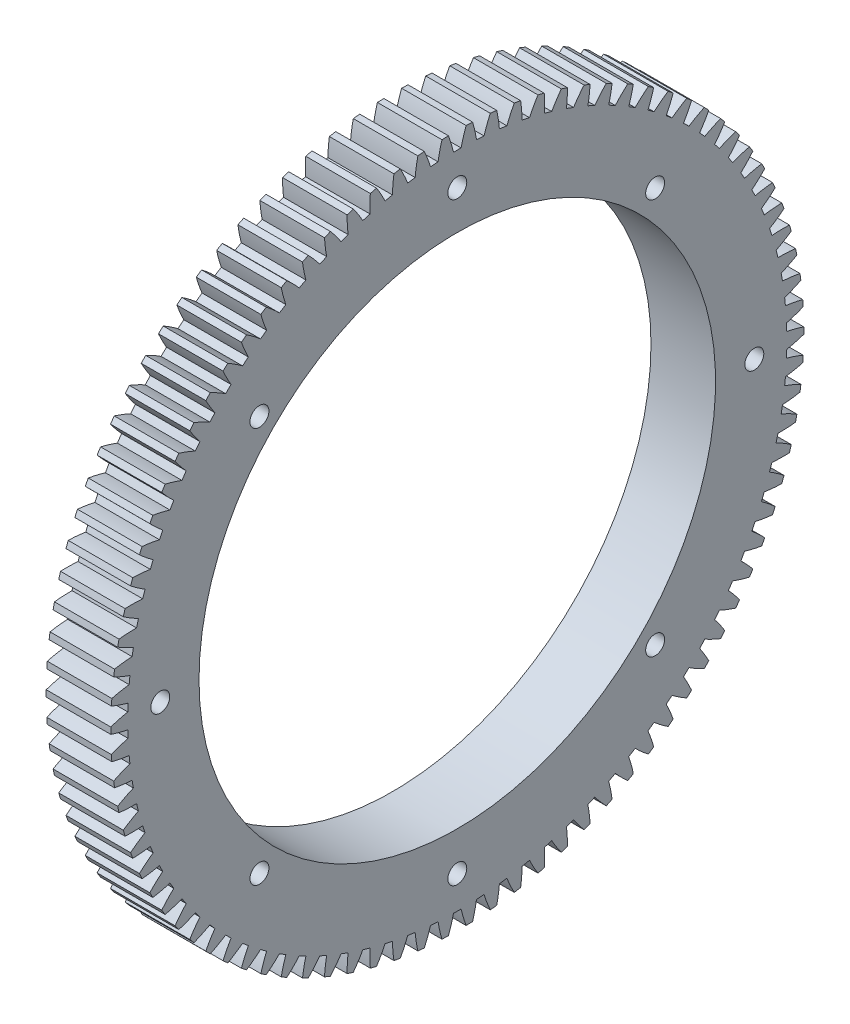
SolidWorks part; units mm, degrees
note: The reader was unsure of these and kept them because the rebuilt part matched: shared geometry of "Sketch1<4>", "Sketch1<5>".
ref_plane "Plane1" through (0, 0, 0) normal (0, 0, 1) x (1, 0, 0)
ref_plane "Plane2" through (0, 0, 0) normal (0, 1, 0) x (1, 0, 0)
ref_plane "Plane3" through (0, 0, 0) normal (1, 0, 0) x (0, 0, -1)
sketch "HoldingSke" plane through (0, 0, 0) normal (0, 1, 0) x (1, 0, 0)
  line L0 (0, 0) -> (0, -0.5714)
  line L1 (-15, 0) -> (100, 0) construction
  line L2 (0, 0) -> (-2.1039, 2.3779)
  line L3 (0, 0) -> (-11.863, 4.5341)
  line L4 (0, 0) -> (0, 8.636)
  line L5 (0, 0) -> (-46.8476, -17.4728)
  line L6 (0, 0) -> (-12.4344, -8.3896)
  line L7 (-2.1039, 2.3779) -> (8.6586, 51.2059)
  line L8 (-76.2, 54.61) -> (-68.8, 54.61)
  line L9 (-67.7845, 28.3722) -> (-49.3413, 33.142)
  line L10 (-76.2, 71.12) -> (104.1128, 71.12)
  line L11 (0, 0) -> (-15, 0)
  line L12 (-76.2, 101.6) -> (-76.147, 101.6)
  line L13 (24.9733, 27.94) -> (52.9518, 28.4284)
  line L14 (24.9733, 27.94) -> (24.9743, 27.94)
  line L15 (24.9733, 27.94) -> (100.4006, 29.5858)
  line L16 (-63.627, -1.75) -> (-12.827, -1.75)
  circle A0 centre (0, 0) radius 60
  circle A1 centre (0, 0) radius 37.5
  circle A2 centre (0, 0) radius 37.5
  circle A3 centre (0, 0) radius 60
  dimension "Num_teeth" = 90
  dimension "Pitch_radius" = 180.3128
  dimension "Width" = 15
  dimension "Thickness" = 15
sketch "BasProSke" plane through (0, 0, 0) normal (0, 1, 0) x (1, 0, 0)
  line L0 (-10, 0) -> (60, 0) construction
  line L1 (0, 0) -> (0, 80.5)
  line L2 (0, 0) -> (15, 0)
  line L3 (15, 0) -> (15, 80.5)
  line L4 (15, 80.5) -> (0, 80.5)
  dimension "Thickness" = 15
  dimension "Diameter" = 161
revolve "Base-Revolve" add sketch "BasProSke" angle 360 about L0
sketch "TooCutSke" plane through (0, 0, 0) normal (1, 0, 0) x (0, 0, -1)
  line L1 (0, 0) -> (0, 107) construction
  line L2 (0, 0) -> (-1.4671, 78.7363) construction
  line L3 (0, 0) -> (-5.4959, 157.3832) construction
  line L4 (-1.4671, 78.7363) -> (-2.748, 78.6916) construction
  arc A0 (0.8759, 76.5565) -> (-0.8759, 76.5565) centre (0, 0) ccw
  arc A1 (2.0714, 80.4988) -> (-2.0714, 80.4988) centre (0, 0) ccw
  circle A2 centre (0, 0) radius 78.75 construction
  circle A3 centre (0, 0) radius 76.2416 construction
  arc A4 (-0.8759, 76.5565) -> (-2.0714, 80.4988) centre (-31.5535, 69.4058) ccw
  arc A5 (2.0714, 80.4988) -> (0.8759, 76.5565) centre (31.5535, 69.4058) ccw
extrude "ToothCut" cut sketch "TooCutSke" along normal through all
fillet "Breaks" [suppressed] radius 0.035
fillet "RootFillets" [suppressed] radius 0.4385
pattern_circular "TeethCuts" count 90 every 4 about axis through (-10, 0, 0) along (1, 0, 0) of "ToothCut", "RootFillets", "Breaks"
sketch "HubNeaOneSke" plane through (0, 0, 0) normal (-1, 0, 0) x (0, 0, 1)
  circle A0 centre (0, 0) radius 37.5
  dimension "Diameter" = 75
extrude "HubNearOne" [suppressed] add sketch "HubNeaOneSke" along normal blind 35.0001
sketch "HubNeaBotSke" plane through (0, 0, 0) normal (-1, 0, 0) x (0, 0, 1)
  circle A0 centre (0, 0) radius 37.5
  dimension "Diameter" = 75
extrude "HubNearBoth" [suppressed] add sketch "HubNeaBotSke" along normal blind 17.5
ref_plane "FarPln" through (15, 0, 0) normal (1, 0, 0) x (0, 0, -1)
sketch "HubFarSke" plane through (15, 0, 0) normal (1, 0, 0) x (0, 0, -1)
  circle A0 centre (0, 0) radius 37.5
  dimension "Diameter" = 75
extrude "HubFar" [suppressed] add sketch "HubFarSke" along normal blind 17.5
sketch "BorSke" plane through (0, 0, 0) normal (1, 0, 0) x (0, 0, -1)
  circle A0 centre (0, 0) radius 60
  dimension "Diameter" = 120
extrude "Bore" cut sketch "BorSke" along normal mid plane 100.0001
sketch "KeySke" plane through (0, 0, 0) normal (1, 0, 0) x (0, 0, -1)
  line L0 (-16, 0) -> (-16, 67.4)
  line L1 (-16, 67.4) -> (16, 67.4)
  line L2 (16, 67.4) -> (16, 0)
  line L3 (0, 0) -> (0, 34) construction
  line L4 (-16, 0) -> (16, 0)
  dimension "Width" = 32
extrude "Keyway" [suppressed] cut sketch "KeySke" along normal mid plane 100.0001
pattern_circular "Keyway2" [suppressed] count 2 every 90 about axis through (-10, 0, 0) along (1, 0, 0)
sketch "Sketch1" plane through (0, 0, 0) normal (1, 0, 0) x (0, 0, -1)
  line L0 (0, 0) -> (0, 69)
  line L1 (0, 0) -> (48.7904, 48.7904) construction
  circle A2 centre (0, 0) radius 69 construction
  circle A3 centre (0, 69) radius 2.2
  circle A4 centre (0, 69) radius 4
  circle A7 centre (69.001, 0.001) radius 4
  circle A8 centre (69.001, 0.001) radius 2.2
  circle A11 centre (0.002, -69) radius 4
  circle A12 centre (0.002, -69) radius 2.2
  circle A15 centre (-68.999, -0.001) radius 4
  circle A16 centre (-68.999, -0.001) radius 2.2
  circle A19 centre (48.7907, 48.7911) radius 4 [skipped]
  circle A20 centre (48.7907, 48.7911) radius 2.2 [skipped]
  circle A21 centre (-48.7901, 48.7897) radius 4 [skipped]
  circle A22 centre (-48.7901, 48.7897) radius 2.2 [skipped]
  circle A23 centre (48.7921, -48.7897) radius 4 [skipped]
  circle A24 centre (48.7921, -48.7897) radius 2.2 [skipped]
  circle A25 centre (-48.7887, -48.7911) radius 4 [skipped]
  circle A26 centre (-48.7887, -48.7911) radius 2.2 [skipped]
  circle A27 centre (0, 0) radius 65 construction
  circle A28 centre (45.9619, 45.9619) radius 2.2
  circle A29 centre (45.9619, 45.9619) radius 4
  circle A30 centre (45.9619, -45.9619) radius 2.2
  circle A31 centre (45.9619, -45.9619) radius 4
  circle A32 centre (-45.9619, -45.9619) radius 2.2
  circle A33 centre (-45.9619, -45.9619) radius 4
  circle A34 centre (-45.9619, 45.9619) radius 2.2
  circle A35 centre (-45.9619, 45.9619) radius 4
  point P30 (0.001, 0)
  point P49 (0, 0)
  dimension "D1" = 8
  dimension "D2" = 138
  dimension "D3" = 4
extrude "Cut-Extrude1" cut sketch "Sketch1" along normal blind 15 contours A8 | A16 | A30 | A34 | A32
extrude "Cut-Extrude2" cut sketch "Sketch1<4>" along normal blind 5
sketch "Sketch1<4>" plane through (0, 0, 0) normal (1, 0, 0) x (0, 0, -1) same geometry as "Sketch1"
extrude "Cut-Extrude3" cut sketch "Sketch1<5>" along normal blind 7 contours A31 A30 | A29 A28 | A35 A34 | A33 A32
sketch "Sketch1<5>" plane through (0, 0, 0) normal (1, 0, 0) x (0, 0, -1) same geometry as "Sketch1"
equation "' \"Module@HoldingSke\" = 6.35"
equation "' \"Num_teeth@HoldingSke\" = 12"
equation "' \"Ap@HoldingSke\" =  20"
equation "' \"Ap@HoldingSke\" = 20"
equation "' \"Width@HoldingSke\" = 0.5 * 25.4"
equation "' \"Hub_dia@HoldingSke\"= 1 * 25.4"
equation "' \"Hub_dia@HoldingSke\" = 1 * 25.4"
equation "' \"Overall_len@HoldingSke\" = 1.0 * 25.4"
equation "' \"Bore@HoldingSke\" = 0.75 * 25.4"
equation "' \"T_dim@HoldingSke\" = 0.1 * 25.4"
equation "' \"Width@KeySke\" = 0.25 * 25.4"
equation "' \"Show_teeth@HoldingSke\" = 13"
equation "' \"Backlash@HoldingSke\" = 0.009 * 25.4"
equation "' \"Addendum_fac@HoldingSke\" = 1.0"
equation "' \"Dedendum_fac@HoldingSke\" = 1.25"
equation "' \"Dedendum_add@HoldingSke\" = 0.00005 * 25.4"
equation "' \"Clearance_fac@HoldingSke\" = 0.25"
equation "\"Pitch@HoldingSke\" = 1 / \"Module@HoldingSke\""
equation "\"Overcut_dia@TooCutSke\" = (\"Num_teeth@HoldingSke\" + 2 * \"Addendum_fac@HoldingSke\") / \"Pitch@HoldingSke\" + 0.002 * 25.4"
equation "\"Pitch_dia@TooCutSke\" = \"Num_teeth@HoldingSke\" / \"Pitch@HoldingSke\""
equation "\"Base_dia@TooCutSke\" = \"Num_teeth@HoldingSke\" / \"Pitch@HoldingSke\" * cos((\"Ap@HoldingSke\"  * 3.14159265 / 180))"
equation "\"Root_dia@TooCutSke\" = (\"Num_teeth@HoldingSke\" + 2) / \"Pitch@HoldingSke\" - 2 * (\"Addendum_fac@HoldingSke\" + \"Dedendum_fac@HoldingSke\") / \"Pitch@HoldingSke\" - \"Dedendum_add@HoldingSke\" * 2"
equation "\"Half_ang@TooCutSke\" = 180 / \"Num_teeth@HoldingSke\""
equation "\"Half_CT@TooCutSke\" = \"Num_teeth@HoldingSke\" / \"Pitch@HoldingSke\" * sin((3.14159265 / 2 / \"Num_teeth@HoldingSke\")) / 2 - 7 * \"Backlash@HoldingSke\" / 4"
equation "\"Flank_rad@TooCutSke\" = \"Num_teeth@HoldingSke\" / \"Pitch@HoldingSke\" / 5"
equation "\"Radius@RootFillets\" = \"Clearance_fac@HoldingSke\" / \"Pitch@HoldingSke\" + \"Dedendum_add@HoldingSke\""
equation "\"Break_rad@Breaks\" = 0.02 / \"Pitch@HoldingSke\""
equation "\"Thickness@HoldingSke\" = \"Width@HoldingSke\""
equation "\"OAL@HoldingSke\" = \"Thickness@HoldingSke\""
equation "\"MHD@HoldingSke\" = (\"Num_teeth@HoldingSke\" + 2) / \"Pitch@HoldingSke\" - 2 * (\"Addendum_fac@HoldingSke\" + \"Dedendum_fac@HoldingSke\")  / \"Pitch@HoldingSke\" - \"Dedendum_add@HoldingSke\" * 2"
equation "\"MBD@HoldingSke\" = (\"Num_teeth@HoldingSke\" + 2) / \"Pitch@HoldingSke\" - 2 * (\"Addendum_fac@HoldingSke\" + \"Dedendum_fac@HoldingSke\")  / \"Pitch@HoldingSke\" - \"Dedendum_add@HoldingSke\" * 2 - 0.002 * 25.4"
equation "\"MHD@HoldingSke\" = ((sgn( \"MHD@HoldingSke\" - \"Hub_dia@HoldingSke\" )-1)*( \"MHD@HoldingSke\" - \"Hub_dia@HoldingSke\" ))/-2+ \"Hub_dia@HoldingSke\""
equation "\"MBD@HoldingSke\" = ((sgn( \"MBD@HoldingSke\" - \"Bore@HoldingSke\" )-1)*( \"MBD@HoldingSke\" - \"Bore@HoldingSke\" ))/-2+ \"Bore@HoldingSke\""
equation "\"OAL@HoldingSke\" = ((sgn( \"OAL@HoldingSke\" - \"Overall_len@HoldingSke\" )+1)*( \"OAL@HoldingSke\" - \"Overall_len@HoldingSke\" ))/2 + \"Overall_len@HoldingSke\" + 0.000002 * 25.4"
equation "\"Num_teeth@TeethCuts\" = int( \"Show_teeth@HoldingSke\" ) + 1"
equation "\"Num_teeth@TeethCuts\" = ((sgn( \"Num_teeth@TeethCuts\" - \"Num_teeth@HoldingSke\" )-1)*( \"Num_teeth@TeethCuts\" - \"Num_teeth@HoldingSke\" ))/-2+ \"Num_teeth@HoldingSke\""
equation "\"Num_teeth@TeethCuts\" = ((sgn( \"Num_teeth@TeethCuts\" - 2.0)+1)*( \"Num_teeth@TeethCuts\" - 2.0))/2 +2.0"
equation "\"Angle@TeethCuts\" = 360.0 / \"Num_teeth@HoldingSke\""
equation "\"Diameter@BasProSke\" = (\"Num_teeth@HoldingSke\" + 2 * \"Addendum_fac@HoldingSke\") / \"Pitch@HoldingSke\""
equation "\"Thickness@BasProSke\"  = \"Thickness@HoldingSke\""
equation "' \"Fillet_rad@BasProSke\" =  \"Thickness@HoldingSke\" * 0.05"
equation "' \"Fillet_rad@BasProSke\" = \"Thickness@HoldingSke\" * 0.05"
equation "\"MHD@HoldingSke\" = ((sgn( \"MHD@HoldingSke\" - \"Root_dia@TooCutSke\" )-1)*( \"MHD@HoldingSke\" - \"Root_dia@TooCutSke\" ))/-2+ \"Root_dia@TooCutSke\""
equation "\"Diameter@HubNeaOneSke\" = \"MHD@HoldingSke\""
equation "\"Length@HubNearOne\" = \"OAL@HoldingSke\" - \"Thickness@BasProSke\""
equation "\"Diameter@HubNeaBotSke\" = \"MHD@HoldingSke\""
equation "\"Length@HubNearBoth\" = ( \"OAL@HoldingSke\" - \"Thickness@BasProSke\" ) / 2.0"
equation "\"Thickness@FarPln\" = \"Thickness@BasProSke\""
equation "\"Diameter@HubFarSke\" = \"MHD@HoldingSke\""
equation "\"Length@HubFar\" = ( \"OAL@HoldingSke\" - \"Thickness@BasProSke\" ) / 2.0"
equation "\"Diameter@BorSke\" = \"MBD@HoldingSke\""
equation "\"D1@Bore\" = \"OAL@HoldingSke\" * 2.0"
equation "\"D1@Keyway\" = \"OAL@HoldingSke\" * 2.0"
equation "\"Offset@KeySke\" = \"T_dim@HoldingSke\" + \"MBD@HoldingSke\" / 2.0"
